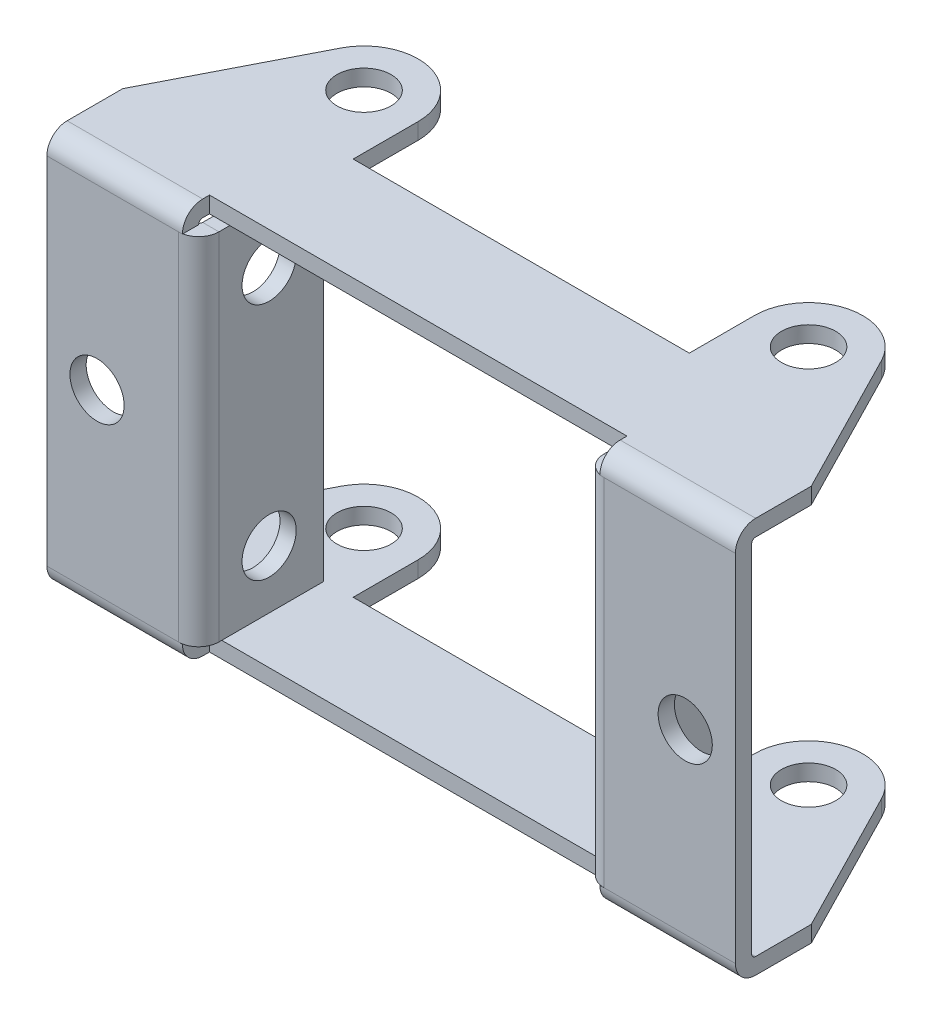
SolidWorks part; units mm, degrees
note: The reader was unsure of these and kept them because the rebuilt part matched: flange length of "Ребро-кромка1", "Ребро-кромка2".
material "AISI 1020"
ref_plane "Спереди" through (0, 0, 0) normal (0, 0, 1) x (1, 0, 0)
ref_plane "Сверху" through (0, 0, 0) normal (0, 1, 0) x (1, 0, 0)
ref_plane "Справа" through (0, 0, 0) normal (1, 0, 0) x (0, 0, -1)
sketch "Эскиз1" plane through (0, 0, 0) normal (0, 0, 1) x (1, 0, 0)
  line L0 (-59.25, 0) -> (59.25, 0) construction
  line L1 (-63.5, -36.5) -> (63.5, -36.5)
  line L2 (-63.5, -36.5) -> (-63.5, 36.5)
  line L3 (-63.5, 36.5) -> (63.5, 36.5)
  line L4 (63.5, -36.5) -> (63.5, 36.5)
  line L5 (-63.5, -36.5) -> (63.5, 36.5) construction
  line L6 (-63.5, 36.5) -> (63.5, -36.5) construction
  circle A0 centre (-54.25, 0) radius 5
  circle A1 centre (54.25, 0) radius 5
  point P0 (0, 0)
  point P12 (0, 0)
  dimension "D3" = 10
  dimension "D1" = 127
  dimension "D2" = 73
  dimension "D4" = 118.5
base flange "Базовая кромка1" sketch "Эскиз1" thickness 3 reverse thickness direction no parameters "D1"=0.74
edge flange "Ребро-кромка1" sketch "Эскиз10" flange profiles "Эскиз10", "Эскиз11" flange angle 90 flange length 46 flange position material inside bend radius 0.74 thickness 3 relief obround parameters "D6"=10, "D8"=1
sketch "Эскиз10" plane through (0, 36.5, -3) normal (0, 1, 0) x (1, 0, 0)
  line L0 (63.5, 0) -> (-63.5, 0) construction
  line L1 (63.5, 0) -> (-63.5, 0)
  line L2 (-63.5, 0) -> (-63.5, 43)
  line L3 (-63.5, 43) -> (63.5, 43)
  line L4 (63.5, 43) -> (63.5, 0)
sketch "Эскиз11" plane through (0, -36.5, -3) normal (0, -1, 0) x (-1, 0, 0)
  line L0 (63.5, 0) -> (-63.5, 0) construction
  line L1 (63.5, 0) -> (-63.5, 0)
  line L2 (-63.5, 0) -> (-63.5, 43)
  line L3 (-63.5, 43) -> (63.5, 43)
  line L4 (63.5, 43) -> (63.5, 0)
bend "EdgeBend1" bend radius 0.74 bend angle 90 parameters "D5"=1
bend "EdgeBend2" bend radius 0.74 bend angle 90 parameters "D5"=2
sketch "Эскиз12" plane through (0, 36.5, 0) normal (0, 1, 0) x (1, 0, 0)
  line L0 (63.5, 14) -> (49.9009, 40.5578)
  line L1 (63.5, 46) -> (63.5, 3) construction
  line L2 (31, 36) -> (31, 24)
  line L3 (31, 24) -> (-31, 24)
  line L4 (0, -995.3649) -> (0, 49004.6351) construction
  line L5 (63.5, 14) -> (63.5, 0)
  line L6 (63.5, 0) -> (38.5, 0)
  line L7 (63.5, 0) -> (-63.5, 0) construction
  line L8 (38.5, 0) -> (38.5, 5)
  line L9 (63.5, 46) -> (-63.5, 46) construction
  line L10 (38.5, 5) -> (-38.5, 5)
  line L11 (-38.5, 0) -> (-38.5, 5)
  line L12 (-63.5, 0) -> (-38.5, 0)
  line L13 (-63.5, 14) -> (-63.5, 0)
  line L14 (-31, 36) -> (-31, 24)
  line L15 (-63.5, 14) -> (-49.9009, 40.5578)
  arc A0 (49.9009, 40.5578) -> (31, 36) centre (41, 36) ccw
  circle A1 centre (41, 36) radius 5
  circle A2 centre (-41, 36) radius 5
  arc A3 (-49.9009, 40.5578) -> (-31, 36) centre (-41, 36) cw
  point P33 (0, 5)
  point P37 (0, 24)
  dimension "D4" = 10
  dimension "D5" = 10
  dimension "D1" = 82
  dimension "D2" = 5
  dimension "D3" = 25
  dimension "D6" = 14
  dimension "D7" = 19
extrude "Вырез-Вытянуть4" cut sketch "Эскиз12" against normal through all flip side to cut
edge flange "Ребро-кромка2" sketch "Эскиз17" flange profiles "Эскиз17", "Эскиз18" flange angle 90 flange length 23 flange position material outside bend radius 0.74 thickness 3 relief none parameters "D6"=10, "D8"=1
sketch "Эскиз17" plane through (38.5, 0, -3) normal (-1, 0, 0) x (0, 1, 0)
  line L2 (-32.76, 0) -> (-32.76, 20)
  line L3 (-32.76, 20) -> (32.76, 20)
  line L4 (32.76, 20) -> (32.76, 0)
  line L7 (-32.76, 0) -> (32.76, 0) construction
  line L8 (-32.76, 0) -> (32.76, 0)
  line L9 (-22.0313, 10) -> (22.0313, 10) construction
  circle A0 centre (-22.0313, 10) radius 5
  circle A1 centre (22.0313, 10) radius 5
  point P8 (0, 10)
  point P9 (32.76, 10)
  dimension "D1" = 10
  dimension "D2" = 10.7287
  dimension "D3" = 10
sketch "Эскиз18" plane through (-38.5, 0, -3) normal (1, 0, 0) x (0, -1, 0)
  line L0 (-32.76, 0) -> (32.76, 0) construction
  line L1 (-32.76, 0) -> (32.76, 0)
  line L2 (-32.76, 0) -> (-32.76, 20)
  line L3 (-32.76, 20) -> (32.76, 20)
  line L4 (32.76, 20) -> (32.76, 0)
  circle A0 centre (22.0313, 10) radius 5 construction
  circle A1 centre (-22.0313, 10) radius 5 construction
  circle A2 centre (22.0313, 10) radius 5
  circle A3 centre (-22.0313, 10) radius 5
bend "EdgeBend3" bend radius 0.74 bend angle 90 parameters "D5"=3
bend "EdgeBend4" bend radius 0.74 bend angle 90 parameters "D5"=4
sketch "Сгиб-Линии1" plane through (0, 0, 0) normal (0, 1, 0) x (1, 0, 0)
sketch "Граничная рамка1" plane through (0, 0, 0) normal (0, 1, 0) x (1, 0, 0)
sheet metal parameters "Листовой металл3" thickness 3 parameters "D1"=0.74
flat pattern "Развертка3" [suppressed]
sketch "Сгиб-Линии2" plane through (0, 0, 0) normal (0, 1, 0) x (1, 0, 0)
sketch "Граничная рамка2" [suppressed] plane through (0, 0, 0) normal (0, 1, 0) x (1, 0, 0)
sheet metal parameters "Листовой металл4" thickness 3 parameters "D1"=0.74
flat pattern "Развертка3" [suppressed]
sketch "Сгиб-Линии2" plane through (0, 0, 0) normal (0, 1, 0) x (1, 0, 0)
sketch "Граничная рамка2" [suppressed] plane through (0, 0, 0) normal (0, 1, 0) x (1, 0, 0)
bend of the flat pattern "Плоское состояние-<EdgeBend1>1"
bend of the flat pattern "Плоское состояние-<EdgeBend2>1"
sheet metal parameters "Листовой металл7" thickness 3 parameters "D1"=0.74
flat pattern "Развертка3" [suppressed]
sketch "Сгиб-Линии2" plane through (0, 0, 0) normal (0, 1, 0) x (1, 0, 0)
sketch "Граничная рамка2" [suppressed] plane through (0, 0, 0) normal (0, 1, 0) x (1, 0, 0)
bend of the flat pattern "Плоское состояние-<EdgeBend1>1"
bend of the flat pattern "Плоское состояние-<EdgeBend2>1"
sheet metal parameters "Листовой металл8" thickness 3 parameters "D1"=0.74
flat pattern "Развертка3" [suppressed]
sketch "Сгиб-Линии2" plane through (0, 0, 0) normal (0, 1, 0) x (1, 0, 0)
sketch "Граничная рамка2" [suppressed] plane through (0, 0, 0) normal (0, 1, 0) x (1, 0, 0)
bend of the flat pattern "Плоское состояние-<EdgeBend1>1"
bend of the flat pattern "Плоское состояние-<EdgeBend2>1"
bend of the flat pattern "Плоское состояние-<EdgeBend3>1"
bend of the flat pattern "Плоское состояние-<EdgeBend4>1"
